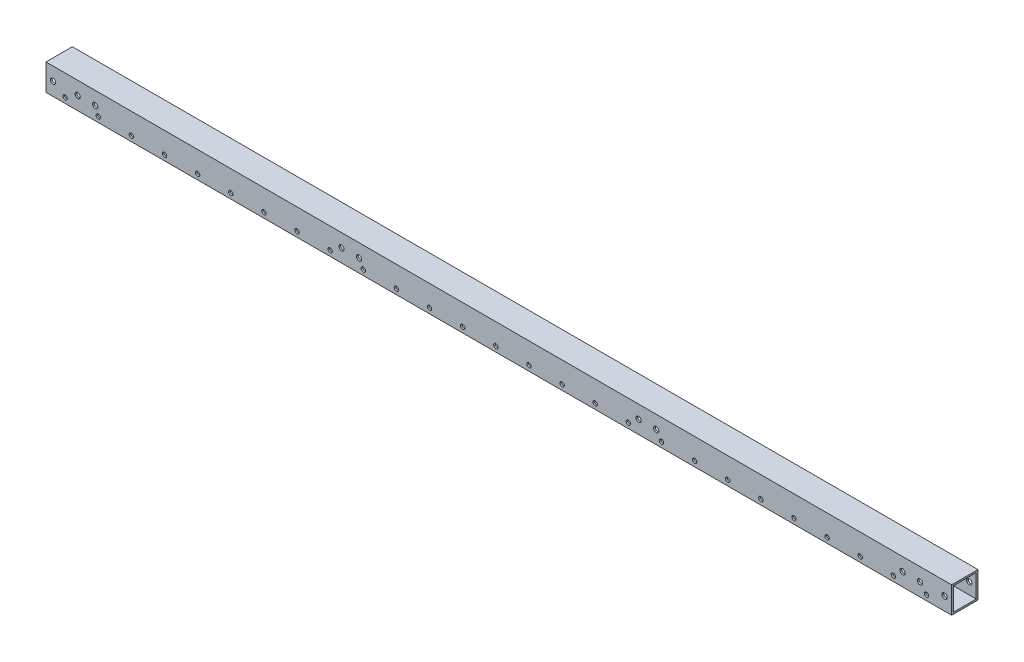
SolidWorks part; units mm, degrees
material "Thornel Mat VMA"
ref_plane "前视基准面" through (0, 0, 0) normal (0, 0, 1) x (1, 0, 0)
ref_plane "上视基准面" through (0, 0, 0) normal (0, 1, 0) x (1, 0, 0)
ref_plane "右视基准面" through (0, 0, 0) normal (1, 0, 0) x (0, 0, -1)
sketch "草图1" plane through (0, 0, 0) normal (1, 0, 0) x (0, 0, -1)
  line L1 (7.5, -7.5) -> (-7.5, -7.5)
  line L2 (7.5, -7.5) -> (7.5, 7.5)
  line L3 (7.5, 7.5) -> (-7.5, 7.5)
  line L4 (-7.5, -7.5) -> (-7.5, 7.5)
  line L5 (7.5, -7.5) -> (-7.5, 7.5) construction
  line L6 (7.5, 7.5) -> (-7.5, -7.5) construction
  line L7 (6.5, -6.5) -> (-6.5, -6.5)
  line L8 (6.5, -6.5) -> (6.5, 6.5)
  line L9 (6.5, 6.5) -> (-6.5, 6.5)
  line L10 (-6.5, -6.5) -> (-6.5, 6.5)
  line L11 (6.5, -6.5) -> (-6.5, 6.5) construction
  line L12 (6.5, 6.5) -> (-6.5, -6.5) construction
  point P0 (0, 0)
  point P6 (0, 0)
  dimension "D1" = 13
  dimension "D2" = 15
extrude "凸台-拉伸1" add sketch "草图1" along normal blind 257.5 and the other way blind 257.5
sketch "草图2" plane through (0, 0, -7.5) normal (0, 0, -1) x (-1, 0, 0)
  line L0 (-257.5, 0) -> (-253.5, 0) construction
  line L1 (-257.5, -7.5) -> (-257.5, 7.5) construction
  line L2 (0, -7.5) -> (0, 67.2037) construction
  line L3 (257.5, -7.5) -> (-257.5, -7.5) construction
  line L4 (-257.5, 6.5) -> (-257.5, -6.5) construction
  circle A53 centre (-243.2168, -4.5) radius 1.25
  circle A54 centre (-253.5, 0) radius 1.5
  circle A55 centre (253.5, 0) radius 1.5
  circle A56 centre (-239.5, 0) radius 1.5
  circle A57 centre (-229.5, 0) radius 1.5
  circle A58 centre (229.5, 0) radius 1.5
  circle A59 centre (239.5, 0) radius 1.5
  circle A60 centre (-89.5, 0) radius 1.5
  circle A61 centre (-79.5, 0) radius 1.5
  circle A62 centre (79.5, 0) radius 1.5
  circle A63 centre (89.5, 0) radius 1.5
  circle A64 centre (-224.3768, -4.5) radius 1.25
  circle A65 centre (-205.5368, -4.5) radius 1.25
  circle A66 centre (-186.6968, -4.5) radius 1.25
  circle A67 centre (-167.8568, -4.5) radius 1.25
  circle A68 centre (-149.0168, -4.5) radius 1.25
  circle A69 centre (-130.1768, -4.5) radius 1.25
  circle A70 centre (-111.3368, -4.5) radius 1.25
  circle A71 centre (-92.4968, -4.5) radius 1.25
  circle A72 centre (-73.6568, -4.5) radius 1.25
  circle A73 centre (-54.8168, -4.5) radius 1.25
  circle A74 centre (-35.9768, -4.5) radius 1.25
  circle A75 centre (-17.1368, -4.5) radius 1.25
  circle A76 centre (1.7032, -4.5) radius 1.25
  circle A77 centre (20.5432, -4.5) radius 1.25
  circle A78 centre (39.3832, -4.5) radius 1.25
  circle A79 centre (58.2232, -4.5) radius 1.25
  circle A80 centre (77.0632, -4.5) radius 1.25
  circle A81 centre (95.9032, -4.5) radius 1.25
  circle A82 centre (114.7432, -4.5) radius 1.25
  circle A83 centre (133.5832, -4.5) radius 1.25
  circle A84 centre (152.4232, -4.5) radius 1.25
  circle A85 centre (171.2632, -4.5) radius 1.25
  circle A86 centre (190.1032, -4.5) radius 1.25
  circle A87 centre (208.9432, -4.5) radius 1.25
  circle A88 centre (227.7832, -4.5) radius 1.25
  circle A89 centre (246.6232, -4.5) radius 1.25
  circle A90 centre (265.4632, -4.5) radius 1.25
  circle A91 centre (284.3032, -4.5) radius 1.25
  circle A92 centre (303.1432, -4.5) radius 1.25
  dimension "D1" = 3
  dimension "D9" = 2.5
  dimension "D2" = 4
  dimension "D3" = 18
  dimension "D4" = 10
  dimension "D5" = 10
  dimension "D6" = 150
  dimension "D7" = 14.2832
  dimension "D8" = 3
  dimension "D11" = 18.84
  dimension "D10" = 30
extrude "切除-拉伸1" cut sketch "草图2" against normal through all
